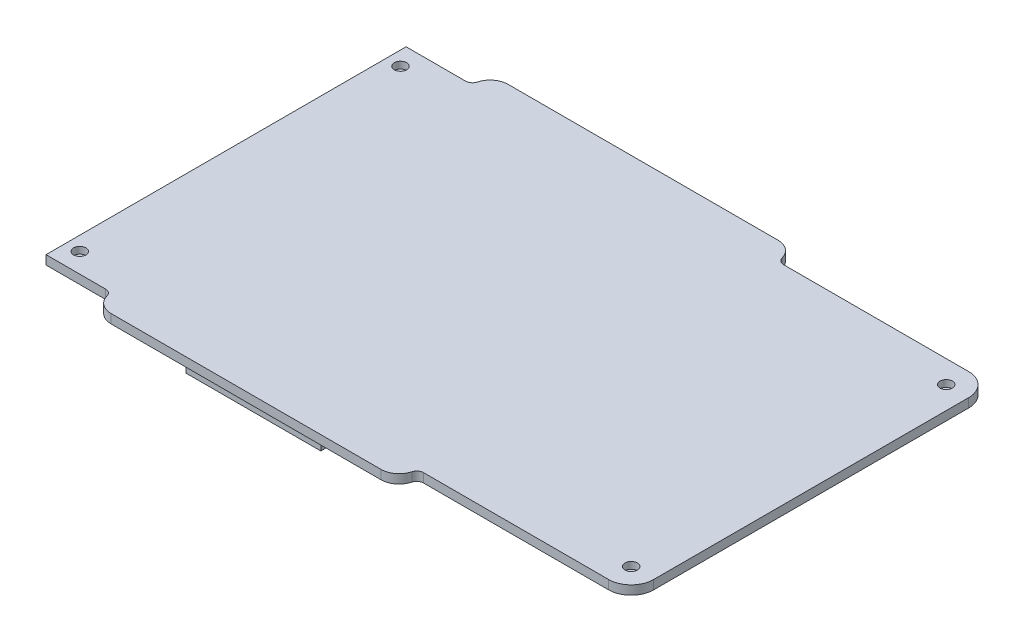
SolidWorks part; units mm, degrees
ref_plane "Front Plane" through (0, 0, 0) normal (0, 0, 1) x (1, 0, 0)
ref_plane "Top Plane" through (0, 0, 0) normal (0, 1, 0) x (1, 0, 0)
ref_plane "Right Plane" through (0, 0, 0) normal (1, 0, 0) x (0, 0, -1)
sketch "Sketch1" plane through (0, 0, 0) normal (0, 1, 0) x (1, 0, 0)
  line L0 (37.08, 160.1) -> (157.08, 160.1)
  line L1 (0, 0) -> (260, 0)
  line L2 (0, 0) -> (0, 160)
  line L3 (0, 160) -> (260, 160)
  line L4 (260, 0) -> (260, 160)
  line L9 (29.5, 168.2) -> (164.72, 168.2)
  line L10 (29.5, 168.2) -> (29.5, 160)
  line L11 (164.72, 168.2) -> (164.72, 160)
  line L12 (0, 80) -> (46.9832, 80)
  line L13 (164.72, -8.2) -> (164.72, 0)
  line L14 (29.5, -8.2) -> (164.72, -8.2)
  line L15 (29.5, -8.2) -> (29.5, 0)
  circle A0 centre (37.08, 160.1) radius 2.75
  circle A1 centre (157.08, 160.1) radius 2.75
  circle A2 centre (157.08, -0.1) radius 2.75
  circle A3 centre (37.08, -0.1) radius 2.75
  dimension "D6" = 5.5
  dimension "D8" = 5.5
  dimension "D1" = 160
  dimension "D2" = 260
  dimension "D3" = 8.1
  dimension "D4" = 37.08
  dimension "D5" = 0.1
  dimension "D7" = 120
  dimension "D9" = 29.5
  dimension "D10" = 135.22
extrude "Boss-Extrude1" add sketch "Sketch1" along normal blind 4 contours A1 L3 A0 L2 L1 L4 | A0 L0 L11 L9 L10 L3 | A1 L0 A0 L3 | L1 A3 L15 L14 L13 A2 | A3 L1 | A3 L1 | A2 L1 | A2 L1 | L3 A0 | L3 A0 | L3 A1 | L3 A1 region at (97.111, 0, -164.2101) region at (37.08, 0, -161.2133) region at (97.08, 0, -160.05) region at (157.08, 0, -161.2133) region at (130.0359, 0, -80) region at (37.08, 0, -158.8786) region at (157.08, 0, -158.8786) region at (97.1107, 0, 4.1662) region at (37.08, 0, -1.1214) region at (37.08, 0, 1.2133) region at (157.08, 0, 1.2133) region at (157.08, 0, -1.1214)
fillet "Fillet1" radius 3 4 edges at (29.5, 2, -160) (164.72, 2, -160) (164.72, 2, 0) (29.5, 2, 0)
fillet "Fillet2" radius 8 4 edges at (29.5, 2, -168.2) (164.72, 2, -168.2) (29.5, 2, 8.2) (164.72, 2, 8.2)
fillet "Fillet3" radius 10 2 edges at (260, 2, -160) (260, 2, 0)
sketch "Sketch2" plane through (0, 0, 0) normal (0, 1, 0) x (1, 0, 0)
  line L0 (0, 0) -> (0, 160) construction
  line L2 (0, 160) -> (26.5, 160) construction
  line L3 (167.72, 160) -> (250, 160) construction
  line L4 (260, 10) -> (260, 150) construction
  line L5 (0, 80) -> (58.0698, 80)
  circle A0 centre (6.25, 151.25) radius 2.75
  circle A1 centre (250, 150) radius 2.75
  circle A2 centre (250, 10) radius 2.75
  circle A3 centre (6.25, 8.75) radius 2.75
  dimension "D1" = 5.5
  dimension "D2" = 5.5
  dimension "D3" = 6.25
  dimension "D4" = 8.75
  dimension "D5" = 10
  dimension "D6" = 10
extrude "Cut-Extrude2" cut sketch "Sketch2" along normal blind 4 contours A0 | A1 | A2 | A3
sketch "Sketch3" plane through (0, 0, 0) normal (0, 1, 0) x (1, 0, 0)
  line L0 (97.11, 168.2) -> (97.11, 165)
  line L1 (67.11, 165) -> (127.11, 165)
  line L2 (67.11, 165) -> (67.11, 161)
  line L3 (67.11, 161) -> (127.11, 161)
  line L4 (127.11, 165) -> (127.11, 161)
  line L5 (37.1377, 168.2) -> (157.0823, 168.2) construction
  line L6 (0, 80) -> (67.1907, 80)
  line L7 (0, 0) -> (0, 160) construction
  line L9 (127.11, -5) -> (127.11, -1)
  line L10 (67.11, -1) -> (127.11, -1)
  line L11 (67.11, -5) -> (67.11, -1)
  line L12 (67.11, -5) -> (127.11, -5)
  line L13 (97.11, -8.2) -> (97.11, -5)
  dimension "D1" = 4
  dimension "D2" = 60
  dimension "D3" = 85
extrude "Boss-Extrude2" add sketch "Sketch3" against normal blind 6 contours L1 L4 L3 L2 | L10 L9 L12 L11
chamfer "Chamfer1" distance 0.5 angle 45 8 edges at (127.11, -6, 3) (97.11, -6, 5) (67.11, -6, 3) (97.11, -6, 1) (67.11, -6, -163) (97.11, -6, -161) (127.11, -6, -163) (97.11, -6, -165)
extrude "Boss-Extrude3" add sketch "Sketch2<3>" along normal blind 1 contours A1 | A2 | A3 | A0
sketch "Sketch2<3>" plane through (0, 0, 0) normal (0, 1, 0) x (1, 0, 0) same geometry as "Sketch2"
